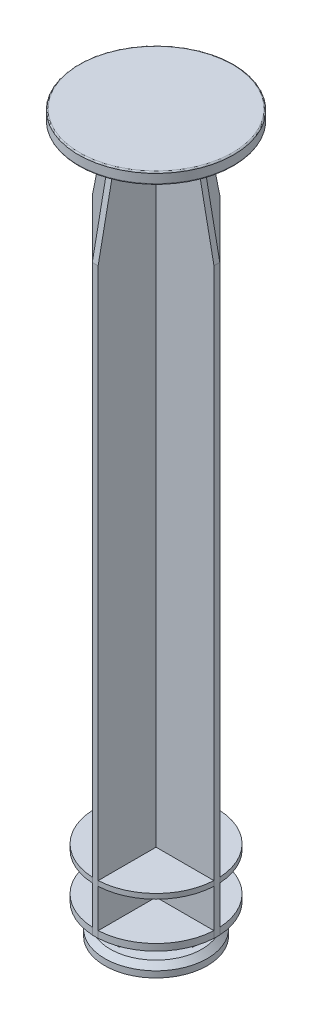
SolidWorks part; units mm, degrees
ref_plane "Front" through (0, 0, 0) normal (0, 0, 1) x (1, 0, 0)
ref_plane "Top" through (0, 0, 0) normal (0, 1, 0) x (1, 0, 0)
ref_plane "Right" through (0, 0, 0) normal (1, 0, 0) x (0, 0, -1)
sketch "Sketch1" plane through (0, 0, 0) normal (0, 0, 1) x (1, 0, 0)
  line L0 (-6.0325, 0) -> (6.0325, 0)
  line L1 (6.0325, 0) -> (6.0325, 4.572)
  line L2 (6.0325, 4.572) -> (9.271, 4.572)
  line L3 (9.271, 4.572) -> (9.271, 93.345)
  line L4 (9.271, 93.345) -> (6.096, 109.22)
  line L5 (6.096, 109.22) -> (-6.096, 109.22)
  line L6 (0, 0) -> (0, 109.22) construction
  line L7 (-6.0325, 0) -> (-6.0325, 4.572)
  line L8 (-6.0325, 4.572) -> (-9.271, 4.572)
  line L9 (-9.271, 4.572) -> (-9.271, 93.345)
  line L10 (-9.271, 93.345) -> (-6.096, 109.22)
  dimension "D1" = 12.065
  dimension "D2" = 18.542
  dimension "D3" = 12.192
  dimension "D4" = 4.572
  dimension "D5" = 109.22
  dimension "D6" = 15.875
extrude "Extrude1" add sketch "Sketch1" along normal mid plane 0.889
ref_axis "Axis1" through (0, 50, 0) along (0, -1, 0)
pattern_circular "CirPattern1" count 2 every 90 about axis through (0, 50, 0) along (0, -1, 0) of "Extrude1"
sketch "Sketch2" plane through (0, 0, 0) normal (0, 0, 1) x (1, 0, 0)
  line L0 (0, 0) -> (0, 22.4129) construction
  line L2 (0, 0) -> (7.8105, 0)
  line L3 (0, 0) -> (0, 1.778)
  line L4 (0, 1.778) -> (7.8105, 1.778)
  line L5 (7.8105, 0) -> (7.8105, 1.778)
  line L6 (-0.4445, 4.572) -> (0.4445, 4.572) construction
  line L7 (0, 4.572) -> (9.271, 4.572)
  line L8 (0, 4.572) -> (0, 5.588)
  line L9 (0, 5.588) -> (9.271, 5.588)
  line L10 (9.271, 4.572) -> (9.271, 5.588)
  line L11 (-0.4445, 109.22) -> (0.4445, 109.22) construction
  line L12 (0, 11.43) -> (9.271, 11.43)
  line L13 (0, 11.43) -> (0, 12.192)
  line L14 (0, 12.192) -> (9.271, 12.192)
  line L15 (9.271, 11.43) -> (9.271, 12.192)
  line L16 (0, 109.22) -> (11.8301, 109.22)
  line L17 (0, 109.22) -> (0, 107.4928)
  line L18 (0, 107.4928) -> (11.8301, 107.4928)
  line L19 (11.8301, 109.22) -> (11.8301, 107.4928)
  dimension "D1" = 15.621
  dimension "D2" = 1.778
  dimension "D3" = 1.016
  dimension "D4" = 0.762
  dimension "D5" = 18.542
  dimension "D6" = 12.192
  dimension "D7" = 1.7272
  dimension "D8" = 23.6601
revolve "Revolve1" add sketch "Sketch2" angle 360 about L0
chamfer "Chamfer1" distance 0.8255 angle 45 1 edges at (7.8105, 1.778, 0)
fillet "Fillet1" radius 1.905 4 edges at (0, 107.4928, -6.4414) (-6.4414, 107.4928, 0) (0, 107.4928, 6.4414) (6.4414, 107.4928, 0)
fillet "Fillet2" radius 0.1905 2 edges at (11.8301, 107.4928, 0) (11.8301, 109.22, 0)
